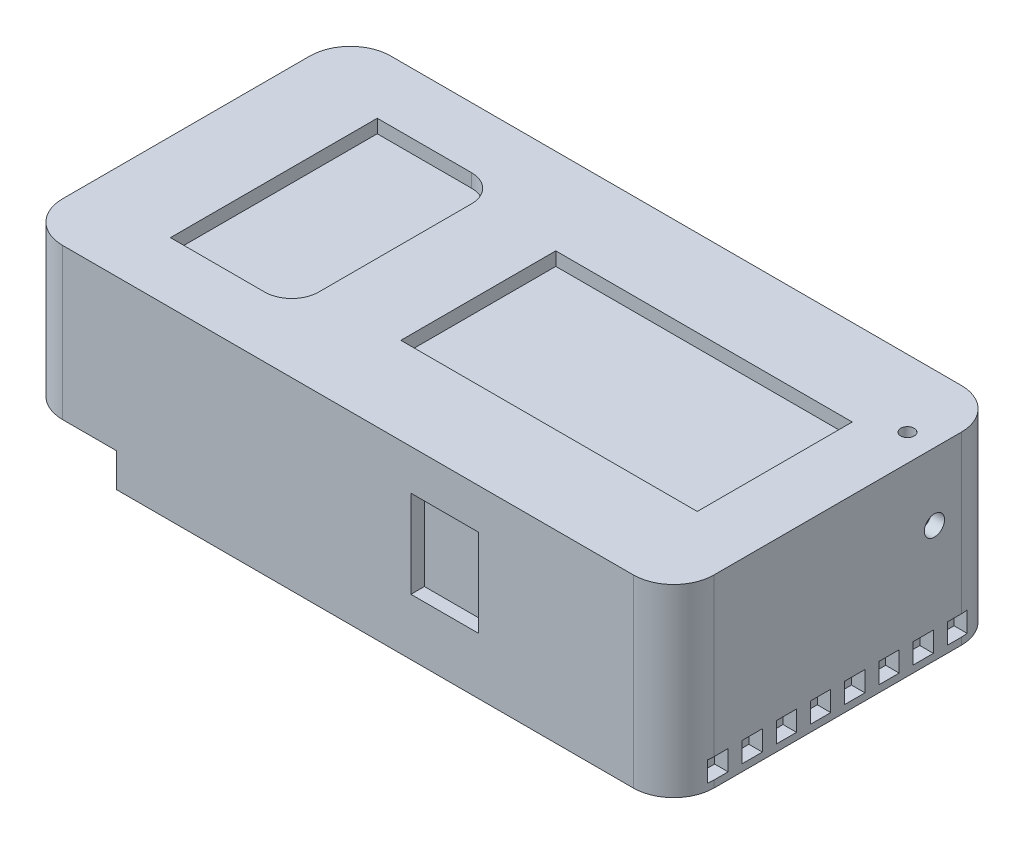
SolidWorks part; units mm, degrees
ref_plane "Front Plane" through (0, 0, 0) normal (0, 0, 1) x (1, 0, 0)
ref_plane "Top Plane" through (0, 0, 0) normal (0, 1, 0) x (1, 0, 0)
ref_plane "Right Plane" through (0, 0, 0) normal (1, 0, 0) x (0, 0, -1)
sketch "Sketch1" plane through (0, 0, 0) normal (0, 1, 0) x (1, 0, 0)
  line L1 (0, 0) -> (48.35, 0)
  line L2 (0, 0) -> (0, 24.35)
  line L3 (0, 24.35) -> (48.35, 24.35)
  line L4 (48.35, 0) -> (48.35, 24.35)
  dimension "D1" = 48.35
  dimension "D2" = 24.35
extrude "Boss-Extrude1" add sketch "Sketch1" along normal blind 13.7
sketch "Sketch2" plane through (0, 13.7, 0) normal (0, 1, 0) x (1, 0, 0)
  line L0 (6.5, 19.85) -> (6.5, 4.5)
  line L1 (6.5, 4.5) -> (13.5, 4.5)
  line L2 (6.5, 19.85) -> (13.5, 19.85)
  line L3 (15.5, 17.85) -> (15.5, 6.5)
  line L4 (0, 24.35) -> (0, 0) construction
  line L5 (48.35, 24.35) -> (0, 24.35) construction
  line L6 (0, 0) -> (48.35, 0) construction
  line L7 (48.35, 0) -> (48.35, 24.35) construction
  line L8 (21.65, 17.95) -> (43.65, 17.95)
  line L9 (21.65, 17.95) -> (21.65, 6.45)
  line L10 (21.65, 6.45) -> (43.65, 6.45)
  line L11 (43.65, 17.95) -> (43.65, 6.45)
  arc A0 (13.5, 19.85) -> (15.5, 17.85) centre (13.5, 17.85) cw
  arc A1 (13.5, 4.5) -> (15.5, 6.5) centre (13.5, 6.5) ccw
  circle A2 centre (46.35, 19.35) radius 0.5
  dimension "D5" = 2
  dimension "D11" = 1
  dimension "D1" = 6.5
  dimension "D2" = 9
  dimension "D3" = 4.5
  dimension "D4" = 4.5
  dimension "D6" = 22
  dimension "D7" = 11.5
  dimension "D8" = 4.7
  dimension "D9" = 6.4
  dimension "D10" = 6.45
  dimension "D12" = 5
  dimension "D13" = 2
extrude "Cut-Extrude1" cut sketch "Sketch2" against normal blind 1
sketch "Sketch3" plane through (0, 0, -24.35) normal (0, 0, -1) x (-1, 0, 0)
  line L0 (0, 13.7) -> (0, 0) construction
  line L1 (-7, 4.7) -> (-12, 4.7)
  line L2 (-7, 4.7) -> (-7, 11.2)
  line L3 (-7, 11.2) -> (-12, 11.2)
  line L4 (-12, 4.7) -> (-12, 11.2)
  line L5 (-48.35, 13.7) -> (0, 13.7) construction
  dimension "D1" = 5
  dimension "D2" = 6.5
  dimension "D3" = 7
  dimension "D4" = 2.5
extrude "Cut-Extrude2" cut sketch "Sketch3" against normal blind 1
sketch "Sketch4" plane through (48.35, 0, 0) normal (1, 0, 0) x (0, 0, -1)
  line L0 (0, 13.7) -> (24.35, 13.7) construction
  line L1 (24.35, 13.7) -> (24.35, 0) construction
  line L2 (5.0786, 2.02) -> (6.5786, 2.02)
  line L3 (2.54, 2.02) -> (4.04, 2.02)
  line L4 (2.54, 2.02) -> (2.54, 0.52)
  line L5 (2.54, 0.52) -> (4.04, 0.52)
  line L6 (4.04, 2.02) -> (4.04, 0.52)
  line L7 (5.0786, 2.02) -> (5.0786, 0.52)
  line L8 (5.0786, 0.52) -> (6.5786, 0.52)
  line L9 (6.5786, 2.02) -> (6.5786, 0.52)
  line L10 (7.6171, 2.02) -> (9.1171, 2.02)
  line L11 (7.6171, 2.02) -> (7.6171, 0.52)
  line L12 (7.6171, 0.52) -> (9.1171, 0.52)
  line L13 (9.1171, 2.02) -> (9.1171, 0.52)
  line L14 (10.1557, 2.02) -> (11.6557, 2.02)
  line L15 (10.1557, 2.02) -> (10.1557, 0.52)
  line L16 (10.1557, 0.52) -> (11.6557, 0.52)
  line L17 (11.6557, 2.02) -> (11.6557, 0.52)
  line L18 (12.6943, 2.02) -> (14.1943, 2.02)
  line L19 (12.6943, 2.02) -> (12.6943, 0.52)
  line L20 (12.6943, 0.52) -> (14.1943, 0.52)
  line L21 (14.1943, 2.02) -> (14.1943, 0.52)
  line L22 (15.2329, 2.02) -> (16.7329, 2.02)
  line L23 (15.2329, 2.02) -> (15.2329, 0.52)
  line L24 (15.2329, 0.52) -> (16.7329, 0.52)
  line L25 (16.7329, 2.02) -> (16.7329, 0.52)
  line L26 (17.7714, 2.02) -> (19.2714, 2.02)
  line L27 (17.7714, 2.02) -> (17.7714, 0.52)
  line L28 (17.7714, 0.52) -> (19.2714, 0.52)
  line L29 (19.2714, 2.02) -> (19.2714, 0.52)
  line L30 (20.31, 2.02) -> (21.81, 2.02)
  line L31 (20.31, 2.02) -> (20.31, 0.52)
  line L32 (20.31, 0.52) -> (21.81, 0.52)
  line L33 (21.81, 2.02) -> (21.81, 0.52)
  line L34 (0, 13.7) -> (0, 0) construction
  line L35 (0, 0) -> (24.35, 0) construction
  circle A0 centre (19.35, 8.7) radius 0.75
  dimension "D1" = 1.5
  dimension "D2" = 5
  dimension "D3" = 5
  dimension "D4" = 1.5
  dimension "D6" = 2.54
  dimension "D7" = 2.54
  dimension "D8" = 2.5386
  dimension "D9" = 0.52
  dimension "D5" = 8
extrude "Cut-Extrude3" cut sketch "Sketch4" against normal blind 1
sketch "Sketch5" plane through (0, 0, 0) normal (0, 0, 1) x (1, 0, 0)
  line L0 (48.35, 13.7) -> (48.35, 0) construction
  line L1 (28.85, 10.7) -> (33.85, 10.7)
  line L2 (28.85, 10.7) -> (28.85, 4.2)
  line L3 (28.85, 4.2) -> (33.85, 4.2)
  line L4 (33.85, 10.7) -> (33.85, 4.2)
  line L5 (0, 13.7) -> (48.35, 13.7) construction
  dimension "D1" = 6.5
  dimension "D2" = 5
  dimension "D3" = 14.5
  dimension "D4" = 3
extrude "Cut-Extrude4" cut sketch "Sketch5" against normal blind 1
sketch "Sketch6" plane through (0, 0, 0) normal (0, -1, 0) x (1, 0, 0)
  line L0 (9, 0) -> (9, -24.35) construction
  line L1 (0, 0) -> (48.35, 0) construction
  line L2 (48.35, -24.35) -> (0, -24.35) construction
  line L3 (0, -24.35) -> (0, 0) construction
  line L5 (0, 0) -> (7, 0)
  line L6 (0, 0) -> (0, -24.35)
  line L7 (0, -24.35) -> (7, -24.35)
  line L8 (7, 0) -> (7, -24.35)
  circle A0 centre (9, -4) radius 1
  circle A1 centre (9, -20.35) radius 1
  dimension "D3" = 2
  dimension "D1" = 9
  dimension "D2" = 7
  dimension "D4" = 4
  dimension "D5" = 4
extrude "Cut-Extrude5" cut sketch "Sketch6" against normal blind 2.5
sketch "Sketch7" plane through (0, 0, 0) normal (-1, 0, 0) x (0, 0, 1)
  line L0 (-15.175, 10.2) -> (-9.175, 10.2) construction
  line L1 (-15.175, 11.7) -> (-9.175, 11.7)
  line L2 (-15.175, 8.7) -> (-9.175, 8.7)
  line L3 (-12.175, 13.7) -> (-12.175, 0) construction
  line L4 (-24.35, 13.7) -> (0, 13.7) construction
  line L5 (-24.35, 0) -> (0, 0) construction
  line L6 (-24.35, 2.5) -> (0, 2.5) construction
  line L7 (-17.175, 2.5) -> (-7.175, 2.5)
  line L8 (-17.175, 2.5) -> (-17.175, 7.65)
  line L9 (-17.175, 7.65) -> (-7.175, 7.65)
  line L10 (-7.175, 2.5) -> (-7.175, 7.65)
  arc A0 (-15.175, 11.7) -> (-15.175, 8.7) centre (-15.175, 10.2) ccw
  arc A1 (-9.175, 8.7) -> (-9.175, 11.7) centre (-9.175, 10.2) ccw
  point P2 (-12.175, 10.2)
  dimension "D2" = 6
  dimension "D1" = 3
  dimension "D3" = 2
  dimension "D4" = 10
  dimension "D5" = 5.15
  dimension "D6" = 5
extrude "Cut-Extrude6" cut sketch "Sketch7" against normal blind 1
fillet "Fillet1" radius 3 4 edges at (0, 8.1, -24.35) (48.35, 6.85, -24.35) (0, 8.1, 0) (48.35, 6.85, 0)
